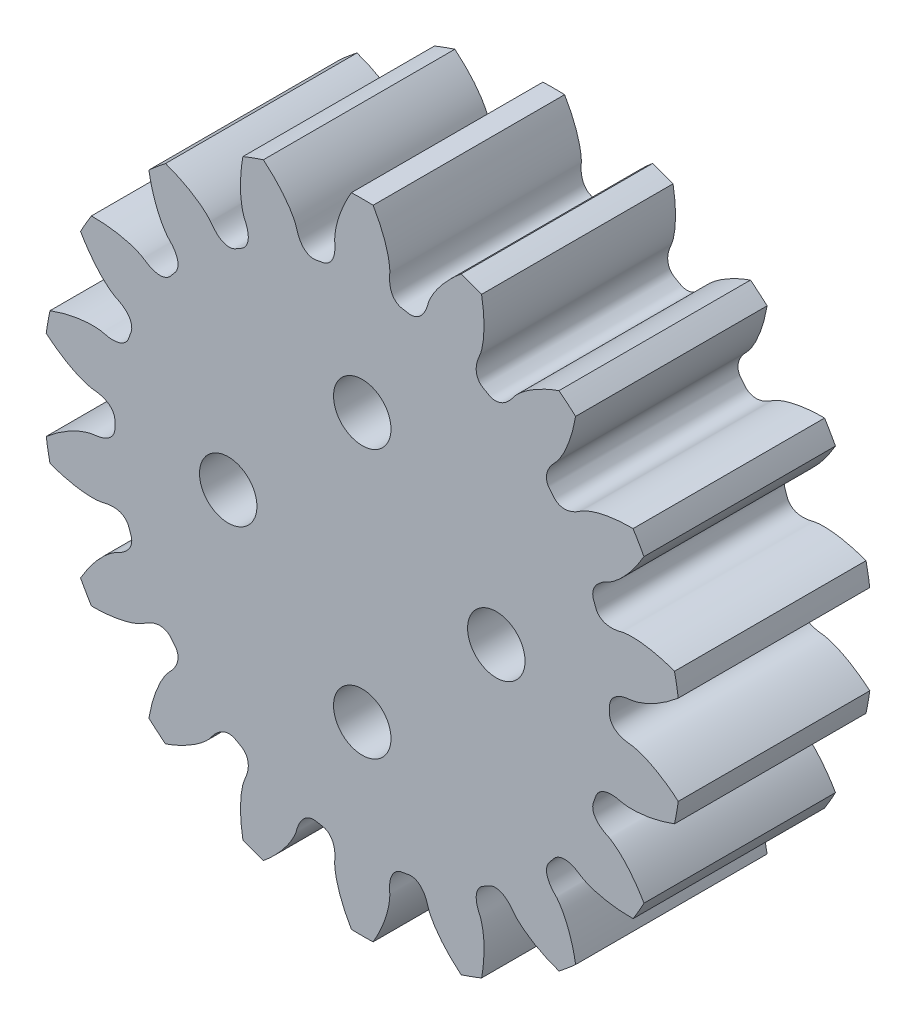
SolidWorks part; units mm, degrees
material "Д16 ГОСТ 4784-97"
ref_plane "FRONT" through (0, 0, 0) normal (0, 0, 1) x (1, 0, 0)
ref_plane "TOP" through (0, 0, 0) normal (0, 1, 0) x (1, 0, 0)
ref_plane "RIGHT" through (0, 0, 0) normal (1, 0, 0) x (0, 0, -1)
ref_axis "Ось1" through (0, 0, 50) along (0, 0, -1)
sketch "SketchRevolveSpurPinion" plane through (0, 0, 0) normal (1, 0, 0) x (0, 0, -1)
  line L0 (0, 0) -> (1, 0) construction
  line L1 (-9.525, 0) -> (-9.525, 16.6667)
  line L2 (-9.525, 16.6667) -> (0.475, 16.6667)
  line L3 (0.475, 16.6667) -> (0.475, 0)
  line L4 (0.475, 0) -> (-9.525, 0)
  dimension "D1" = 10
revolve "SpurPinion" add sketch "SketchRevolveSpurPinion" angle 360 about L0
sketch "SketchToothSpurPinion" plane through (0, 0, 0) normal (0, 0, 1) x (1, 0, 0)
  arc A0 (16.5775, 2.3974) -> (16.5775, -2.3974) centre (0, 0) cw
  spline S0 degree 3 poles (16.5775, -2.3974) (16.3745, -2.2215) (16.101, -2.0047) (15.752, -1.7646) (15.5625, -1.643) (15.3817, -1.5351) (15.2102, -1.44) (15.0487, -1.3571) (14.8977, -1.2856) (14.7578, -1.2248) (14.6296, -1.1738) (14.5135, -1.1319) (14.4099, -1.0983) (14.3192, -1.072) (14.2418, -1.0522) (14.178, -1.038) (14.128, -1.0286) (14.0922, -1.023) (14.0706, -1.0202) (14.028, -1.0163) (13.977, -1.0123) (13.9132, -1.0045) (13.8673, -0.998) (13.8222, -0.9906) (13.7779, -0.9825) (13.7345, -0.9735) (13.6919, -0.9636) (13.65, -0.9529) (13.6089, -0.9412) (13.5686, -0.9287) (13.529, -0.9152) (13.4901, -0.9006) (13.4519, -0.885) (13.4143, -0.8683) (13.3773, -0.8504) (13.3409, -0.8312) (13.3051, -0.8105) (13.2699, -0.7883) (13.2352, -0.7644) (13.2011, -0.7387) (13.1677, -0.7108) (13.1351, -0.6806) (13.1033, -0.6479) (13.0727, -0.6124) (13.0434, -0.5739) (13.0158, -0.5323) (12.9904, -0.4873) (12.9678, -0.4391) (12.9484, -0.3876) (12.933, -0.3332) (12.922, -0.2765) (12.9166, -0.2227) (12.9143, -0.1303) (12.9186, 0) (12.9143, 0.1303) (12.9166, 0.2227) (12.922, 0.2765) (12.933, 0.3332) (12.9484, 0.3876) (12.9678, 0.4391) (12.9904, 0.4873) (13.0158, 0.5323) (13.0434, 0.5739) (13.0727, 0.6124) (13.1033, 0.6479) (13.1351, 0.6806) (13.1677, 0.7108) (13.2011, 0.7387) (13.2352, 0.7644) (13.2699, 0.7883) (13.3051, 0.8105) (13.3409, 0.8312) (13.3773, 0.8504) (13.4143, 0.8683) (13.4519, 0.885) (13.4901, 0.9006) (13.529, 0.9152) (13.5686, 0.9287) (13.6089, 0.9412) (13.65, 0.9529) (13.6919, 0.9636) (13.7345, 0.9735) (13.7779, 0.9825) (13.8222, 0.9906) (13.8673, 0.998) (13.9132, 1.0045) (13.977, 1.0123) (14.028, 1.0163) (14.0706, 1.0202) (14.0922, 1.023) (14.128, 1.0286) (14.178, 1.038) (14.2418, 1.0522) (14.3192, 1.072) (14.4099, 1.0983) (14.5135, 1.1319) (14.6296, 1.1738) (14.7578, 1.2248) (14.8977, 1.2856) (15.0487, 1.3571) (15.2102, 1.44) (15.3817, 1.5351) (15.5625, 1.643) (15.752, 1.7646) (16.101, 2.0047) (16.3745, 2.2215) (16.5775, 2.3974) knots 0 0 0 0 0.086682 0.112454 0.136665 0.159314 0.1804 0.199925 0.217888 0.234288 0.249127 0.262404 0.274119 0.284272 0.292862 0.299891 0.305358 0.309263 0.311606 0.312387 0.323046 0.328118 0.333109 0.338022 0.342862 0.347631 0.352335 0.356978 0.361567 0.366106 0.370604 0.375067 0.379505 0.383926 0.388341 0.392762 0.397202 0.401675 0.406197 0.410784 0.415455 0.420228 0.425122 0.430157 0.43535 0.440715 0.446262 0.451994 0.457907 0.463985 0.470202 0.476522 0.481419 0.5 0.518581 0.523478 0.529798 0.536015 0.542093 0.548006 0.553738 0.559285 0.56465 0.569843 0.574878 0.579772 0.584545 0.589216 0.593803 0.598325 0.602798 0.607238 0.611659 0.616074 0.620495 0.624933 0.629396 0.633894 0.638433 0.643022 0.647665 0.652369 0.657138 0.661978 0.666891 0.671882 0.676954 0.687613 0.688394 0.690737 0.694642 0.700109 0.707138 0.715728 0.725881 0.737596 0.750873 0.765712 0.782112 0.800075 0.8196 0.840686 0.863335 0.887546 0.913318 1 1 1 1
extrude "ToothExtrudeCutSpurPinion" cut sketch "SketchToothSpurPinion" against normal blind 9.525 and the other way blind 9.525
pattern_circular "PatternSpurPinion" count 18 every 20 about axis through (0, 0, 50) along (0, 0, -1) of "ToothExtrudeCutSpurPinion"
sketch "BoreRevolveSketch" plane through (0, 0, 0) normal (1, 0, 0) x (0, 0, -1)
  line L0 (0, 0) -> (1, 0) construction
  line L1 (-9.525, 0) -> (9.525, 0)
  line L2 (9.525, 0) -> (9.525, 6.35)
  line L3 (9.525, 6.35) -> (-9.525, 6.35)
  line L4 (-9.525, 6.35) -> (-9.525, 0)
  dimension "TaperSide1" = 6.35
  dimension "TaperSide2" = 6.35
sketch "AuxiliarySketchSpurPinion" plane through (0, 0, 0) normal (0, 0, 1) x (1, 0, 0)
  circle A0 centre (0, 0) radius 15 construction
  circle A1 centre (0, 0) radius 14.0954 construction
  circle A2 centre (0, 0) radius 14.0954 construction
  circle A3 centre (0, 0) radius 16.6667 construction
  circle A4 centre (0, 0) radius 12.9167 construction
  dimension "PitchDiameter" = 30
  dimension "BaseDiameter" = 28.1908
  dimension "FormDiameter" = 28.1908
  dimension "MajorDiameter" = 33.3333
  dimension "MinorDiameter" = 25.8333
sketch "Эскиз5" plane through (0, 0, 9.525) normal (0, 0, 1) x (1, 0, 0)
  circle A0 centre (0, 0) radius 7 construction
  circle A1 centre (0, 0) radius 8.5 construction
  circle A2 centre (0, 7) radius 1.5
  circle A3 centre (7, 0) radius 1.5
  circle A4 centre (0, -7) radius 1.5
  circle A5 centre (-7, 0) radius 1.5
  dimension "D1" = 17
  dimension "D2" = 14
extrude "Вырез-Вытянуть2" cut sketch "Эскиз5" against normal blind 5
